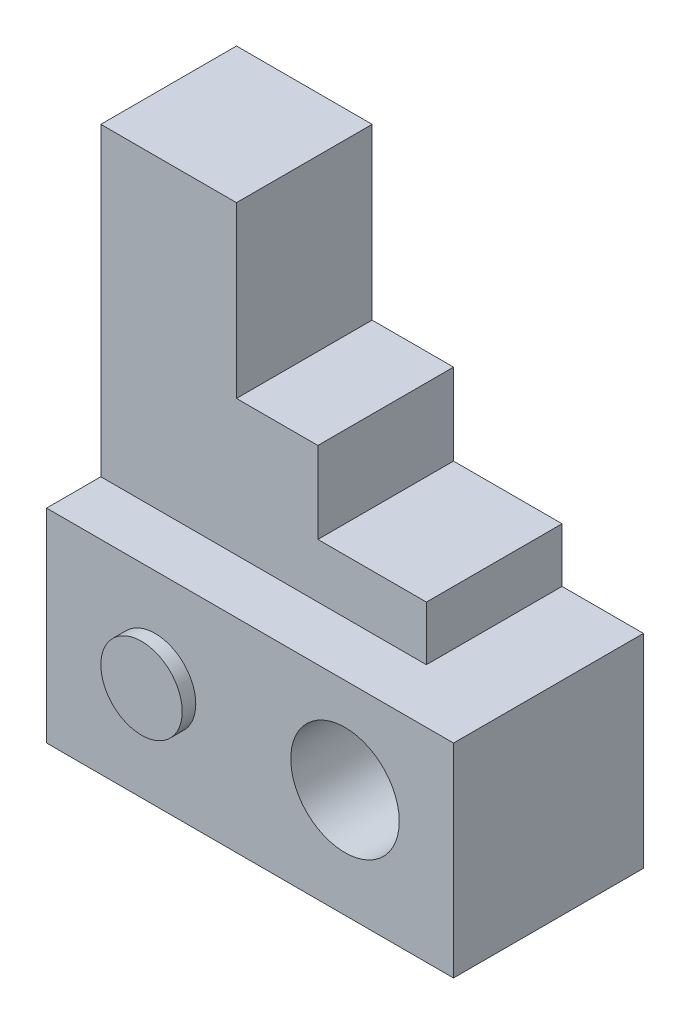
SolidWorks part; units mm, degrees
material "Aluminum Bronze"
ref_plane "Front Plane" through (0, 0, 0) normal (0, 0, 1) x (1, 0, 0)
ref_plane "Top Plane" through (0, 0, 0) normal (0, 1, 0) x (1, 0, 0)
ref_plane "Right Plane" through (0, 0, 0) normal (1, 0, 0) x (0, 0, -1)
sketch "Sketch1" plane through (0, 0, 0) normal (0, 0, 1) x (1, 0, 0)
  line L1 (0, 0) -> (60, 0)
  line L2 (0, 0) -> (0, 30)
  line L3 (0, 30) -> (60, 30)
  line L4 (60, 0) -> (60, 30)
  circle A0 centre (44, 16) radius 8
  dimension "D3" = 16
  dimension "D1" = 60
  dimension "D2" = 30
  dimension "D4" = 16
  dimension "D5" = 16
extrude "Boss-Extrude1" add sketch "Sketch1" along normal blind 28
sketch "Sketch2" plane through (0, 0, 0) normal (0, 0, 1) x (1, 0, 0)
  line L0 (0, 30) -> (0, 75)
  line L1 (0, 75) -> (20, 75)
  line L2 (20, 75) -> (20, 50)
  line L3 (20, 50) -> (32, 50)
  line L4 (32, 50) -> (32, 38)
  line L5 (32, 38) -> (48, 38)
  line L6 (48, 38) -> (48, 30)
  line L7 (60, 30) -> (0, 30) construction
  line L8 (48, 30) -> (0, 30)
  line L9 (0, 0) -> (60, 0) construction
  line L10 (60, 0) -> (60, 30) construction
  dimension "D1" = 75
  dimension "D2" = 12
  dimension "D3" = 12
  dimension "D4" = 12
  dimension "D5" = 20
  dimension "D6" = 20
extrude "Boss-Extrude2" add sketch "Sketch2" along normal blind 20
sketch "Sketch3" plane through (0, 0, 28) normal (0, 0, 1) x (1, 0, 0)
  line L0 (0, 0) -> (60, 0) construction
  line L1 (0, 0) -> (0, 30) construction
  circle A0 centre (16, 16) radius 6
  dimension "D3" = 12
  dimension "D1" = 16
  dimension "D2" = 16
extrude "Boss-Extrude3" add sketch "Sketch3" along normal blind 2
